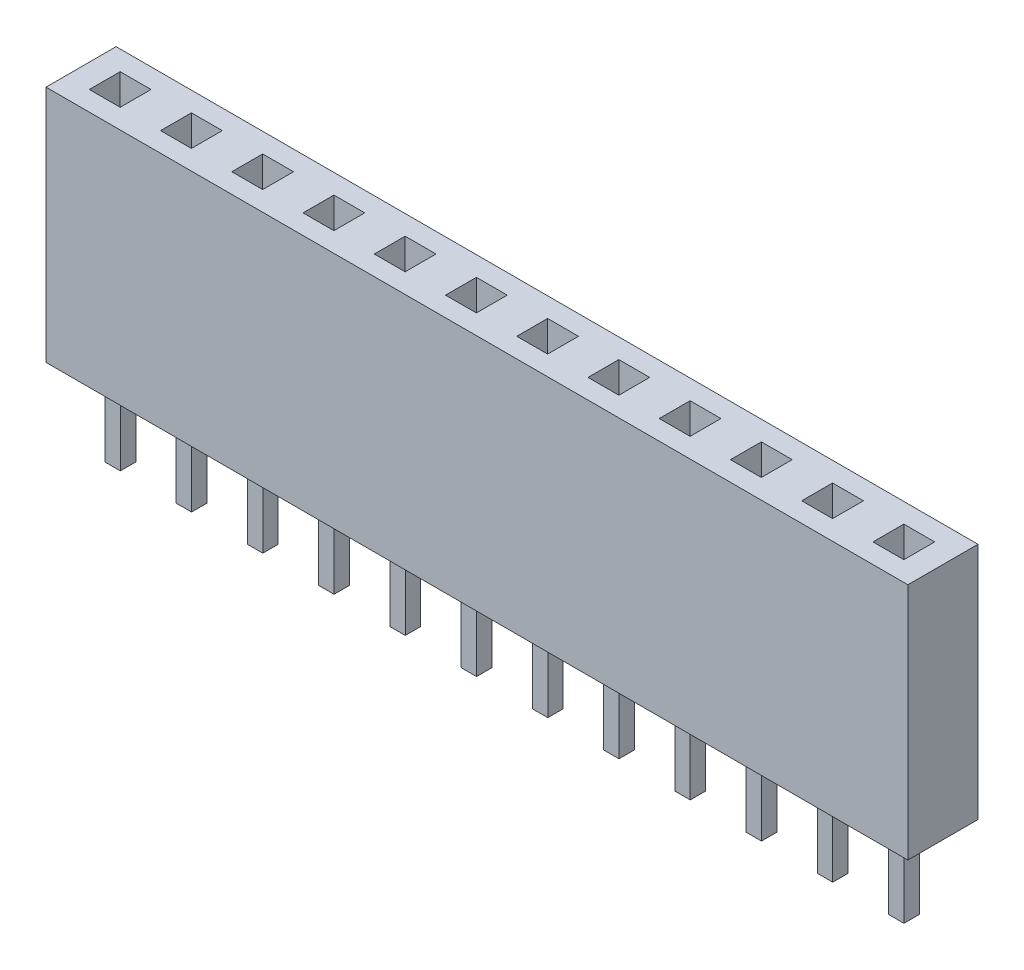
SolidWorks part; units mm, degrees
ref_plane "Front Plane" through (0, 0, 0) normal (0, 0, 1) x (1, 0, 0)
ref_plane "Top Plane" through (0, 0, 0) normal (0, 1, 0) x (1, 0, 0)
ref_plane "Right Plane" through (0, 0, 0) normal (1, 0, 0) x (0, 0, -1)
sketch "Sketch1" plane through (0, 0, 0) normal (0, 0, 1) x (1, 0, 0)
  line L1 (0, 0) -> (30.73, 0)
  line L2 (0, 0) -> (0, 8.5)
  line L3 (0, 8.5) -> (30.73, 8.5)
  line L4 (30.73, 0) -> (30.73, 8.5)
  dimension "D1" = 8.5
  dimension "D2" = 30.73
extrude "Boss-Extrude1" add sketch "Sketch1" along normal mid plane 2.5
sketch "Sketch2" plane through (0, 0, 0) normal (0, -1, 0) x (1, 0, 0)
  line L0 (0, 0) -> (30.73, 0) construction
  line L1 (30.73, 1.25) -> (30.73, -1.25) construction
  line L2 (3.385, -0.55) -> (4.485, -0.55)
  line L3 (0.845, -0.55) -> (1.945, -0.55)
  line L4 (0.845, -0.55) -> (0.845, 0.55)
  line L5 (0.845, 0.55) -> (1.945, 0.55)
  line L6 (1.945, -0.55) -> (1.945, 0.55)
  line L7 (0.845, -0.55) -> (1.945, 0.55) construction
  line L8 (0.845, 0.55) -> (1.945, -0.55) construction
  line L9 (3.385, -0.55) -> (3.385, 0.55)
  line L10 (3.385, 0.55) -> (4.485, 0.55)
  line L11 (4.485, -0.55) -> (4.485, 0.55)
  line L12 (3.385, -0.55) -> (4.485, 0.55) construction
  line L13 (3.385, 0.55) -> (4.485, -0.55) construction
  line L14 (5.925, -0.55) -> (7.025, -0.55)
  line L15 (5.925, -0.55) -> (5.925, 0.55)
  line L16 (5.925, 0.55) -> (7.025, 0.55)
  line L17 (7.025, -0.55) -> (7.025, 0.55)
  line L18 (5.925, -0.55) -> (7.025, 0.55) construction
  line L19 (5.925, 0.55) -> (7.025, -0.55) construction
  line L20 (8.465, -0.55) -> (9.565, -0.55)
  line L21 (8.465, -0.55) -> (8.465, 0.55)
  line L22 (8.465, 0.55) -> (9.565, 0.55)
  line L23 (9.565, -0.55) -> (9.565, 0.55)
  line L24 (8.465, -0.55) -> (9.565, 0.55) construction
  line L25 (8.465, 0.55) -> (9.565, -0.55) construction
  line L26 (11.005, -0.55) -> (12.105, -0.55)
  line L27 (11.005, -0.55) -> (11.005, 0.55)
  line L28 (11.005, 0.55) -> (12.105, 0.55)
  line L29 (12.105, -0.55) -> (12.105, 0.55)
  line L30 (11.005, -0.55) -> (12.105, 0.55) construction
  line L31 (11.005, 0.55) -> (12.105, -0.55) construction
  line L32 (13.545, -0.55) -> (14.645, -0.55)
  line L33 (13.545, -0.55) -> (13.545, 0.55)
  line L34 (13.545, 0.55) -> (14.645, 0.55)
  line L35 (14.645, -0.55) -> (14.645, 0.55)
  line L36 (13.545, -0.55) -> (14.645, 0.55) construction
  line L37 (13.545, 0.55) -> (14.645, -0.55) construction
  line L38 (16.085, -0.55) -> (17.185, -0.55)
  line L39 (16.085, -0.55) -> (16.085, 0.55)
  line L40 (16.085, 0.55) -> (17.185, 0.55)
  line L41 (17.185, -0.55) -> (17.185, 0.55)
  line L42 (16.085, -0.55) -> (17.185, 0.55) construction
  line L43 (16.085, 0.55) -> (17.185, -0.55) construction
  line L44 (18.625, -0.55) -> (19.725, -0.55)
  line L45 (18.625, -0.55) -> (18.625, 0.55)
  line L46 (18.625, 0.55) -> (19.725, 0.55)
  line L47 (19.725, -0.55) -> (19.725, 0.55)
  line L48 (18.625, -0.55) -> (19.725, 0.55) construction
  line L49 (18.625, 0.55) -> (19.725, -0.55) construction
  line L54 (21.165, -0.55) -> (22.265, -0.55)
  line L55 (21.165, -0.55) -> (21.165, 0.55)
  line L60 (21.165, 0.55) -> (22.265, 0.55)
  line L61 (22.265, -0.55) -> (22.265, 0.55)
  line L66 (21.165, -0.55) -> (22.265, 0.55) construction
  line L67 (21.165, 0.55) -> (22.265, -0.55) construction
  line L72 (23.705, -0.55) -> (24.805, -0.55)
  line L73 (23.705, -0.55) -> (23.705, 0.55)
  line L78 (1.395, 0) -> (3.935, 0) construction
  line L79 (23.705, 0.55) -> (24.805, 0.55)
  line L80 (24.805, -0.55) -> (24.805, 0.55)
  line L81 (23.705, -0.55) -> (24.805, 0.55) construction
  line L82 (23.705, 0.55) -> (24.805, -0.55) construction
  line L83 (26.245, -0.55) -> (27.345, -0.55)
  line L84 (26.245, -0.55) -> (26.245, 0.55)
  line L85 (26.245, 0.55) -> (27.345, 0.55)
  line L86 (27.345, -0.55) -> (27.345, 0.55)
  line L87 (26.245, -0.55) -> (27.345, 0.55) construction
  line L88 (26.245, 0.55) -> (27.345, -0.55) construction
  line L89 (28.785, -0.55) -> (29.885, -0.55)
  line L90 (28.785, -0.55) -> (28.785, 0.55)
  line L91 (28.785, 0.55) -> (29.885, 0.55)
  line L92 (29.885, -0.55) -> (29.885, 0.55)
  line L93 (28.785, -0.55) -> (29.885, 0.55) construction
  line L94 (28.785, 0.55) -> (29.885, -0.55) construction
  point P5 (1.395, 0)
  point P11 (21.715, 0)
  point P12 (3.935, 0)
  point P17 (6.475, 0)
  point P22 (9.015, 0)
  point P27 (11.555, 0)
  point P32 (14.095, 0)
  point P37 (16.635, 0)
  point P42 (19.175, 0)
  point P51 (24.255, 0)
  point P56 (26.795, 0)
  point P61 (29.335, 0)
  dimension "D1" = 1.1
  dimension "D3" = 1.395
  dimension "D4" = 2.54
  dimension "D2" = 12
extrude "Cut-Extrude1" cut sketch "Sketch2" against normal through all contours L3 L6 L5 L4 | L2 L11 L10 L9 | L14 L17 L16 L15 | L20 L23 L22 L21 | L26 L29 L28 L27 | L32 L35 L34 L33 | L38 L41 L40 L39 | L44 L47 L46 L45 | L60 L61 L54 L55 | L79 L80 L72 L73 | L85 L86 L83 L84 | L91 L92 L89 L90 region at (3.935, 0, 0) region at (1.395, 0, 0) region at (6.475, 0, 0) region at (9.015, 0, 0) region at (11.555, 0, 0) region at (14.095, 0, 0) region at (16.635, 0, 0) region at (19.175, 0, 0)
sketch "Sketch3" plane through (0, 0, 0) normal (0, -1, 0) x (1, 0, 0)
  line L1 (0, 1.25) -> (30.73, 1.25)
  line L2 (0, 1.25) -> (0, -1.25)
  line L3 (0, -1.25) -> (30.73, -1.25)
  line L4 (30.73, 1.25) -> (30.73, -1.25)
extrude "Boss-Extrude2" add sketch "Sketch3" against normal blind 1
sketch "Sketch4" plane through (0, 0, 0) normal (0, -1, 0) x (1, 0, 0)
  line L0 (1.125, 0) -> (1.675, 0) construction
  line L1 (1.125, 0.275) -> (1.675, 0.275)
  line L2 (1.125, 0.275) -> (1.125, -0.275)
  line L3 (1.125, -0.275) -> (1.675, -0.275)
  line L4 (1.675, 0.275) -> (1.675, -0.275)
  line L5 (0, 0) -> (30.73, 0) construction
  line L6 (30.73, 1.25) -> (30.73, -1.25) construction
  line L7 (0, 1.25) -> (0, -1.25) construction
  line L8 (3.665, 0.275) -> (3.665, -0.275)
  line L9 (3.665, 0.275) -> (4.215, 0.275)
  line L10 (3.665, -0.275) -> (4.215, -0.275)
  line L11 (4.215, 0.275) -> (4.215, -0.275)
  line L12 (6.205, 0.275) -> (6.205, -0.275)
  line L13 (6.205, 0.275) -> (6.755, 0.275)
  line L14 (6.205, -0.275) -> (6.755, -0.275)
  line L15 (6.755, 0.275) -> (6.755, -0.275)
  line L16 (8.745, 0.275) -> (8.745, -0.275)
  line L17 (8.745, 0.275) -> (9.295, 0.275)
  line L18 (8.745, -0.275) -> (9.295, -0.275)
  line L19 (9.295, 0.275) -> (9.295, -0.275)
  line L20 (11.285, 0.275) -> (11.285, -0.275)
  line L21 (11.285, 0.275) -> (11.835, 0.275)
  line L22 (11.285, -0.275) -> (11.835, -0.275)
  line L23 (11.835, 0.275) -> (11.835, -0.275)
  line L24 (13.825, 0.275) -> (13.825, -0.275)
  line L25 (13.825, 0.275) -> (14.375, 0.275)
  line L26 (13.825, -0.275) -> (14.375, -0.275)
  line L27 (14.375, 0.275) -> (14.375, -0.275)
  line L28 (16.365, 0.275) -> (16.365, -0.275)
  line L29 (16.365, 0.275) -> (16.915, 0.275)
  line L30 (16.365, -0.275) -> (16.915, -0.275)
  line L31 (16.915, 0.275) -> (16.915, -0.275)
  line L32 (18.905, 0.275) -> (18.905, -0.275)
  line L33 (18.905, 0.275) -> (19.455, 0.275)
  line L34 (18.905, -0.275) -> (19.455, -0.275)
  line L35 (19.455, 0.275) -> (19.455, -0.275)
  line L52 (1.125, 0.275) -> (3.665, 0.275) construction
  line L53 (21.445, 0.275) -> (21.445, -0.275)
  line L54 (21.445, 0.275) -> (21.995, 0.275)
  line L55 (21.445, -0.275) -> (21.995, -0.275)
  line L56 (21.995, 0.275) -> (21.995, -0.275)
  line L57 (23.985, 0.275) -> (23.985, -0.275)
  line L58 (23.985, 0.275) -> (24.535, 0.275)
  line L59 (23.985, -0.275) -> (24.535, -0.275)
  line L60 (24.535, 0.275) -> (24.535, -0.275)
  line L61 (26.525, 0.275) -> (26.525, -0.275)
  line L62 (26.525, 0.275) -> (27.075, 0.275)
  line L63 (26.525, -0.275) -> (27.075, -0.275)
  line L64 (27.075, 0.275) -> (27.075, -0.275)
  line L65 (29.065, 0.275) -> (29.065, -0.275)
  line L66 (29.065, 0.275) -> (29.615, 0.275)
  line L67 (29.065, -0.275) -> (29.615, -0.275)
  line L68 (29.615, 0.275) -> (29.615, -0.275)
  point P6 (1.4, 0)
  dimension "D1" = 0.55
  dimension "D2" = 1.4
  dimension "D4" = 2.54
  dimension "D3" = 12
extrude "Boss-Extrude3" add sketch "Sketch4" along normal blind 3 separate body
ref_axis "Axis1" through (1.395, 0, 0) along (0, -1, 0)
ref_axis "Axis2" through (29.335, 0, 0) along (0, -1, 0)
